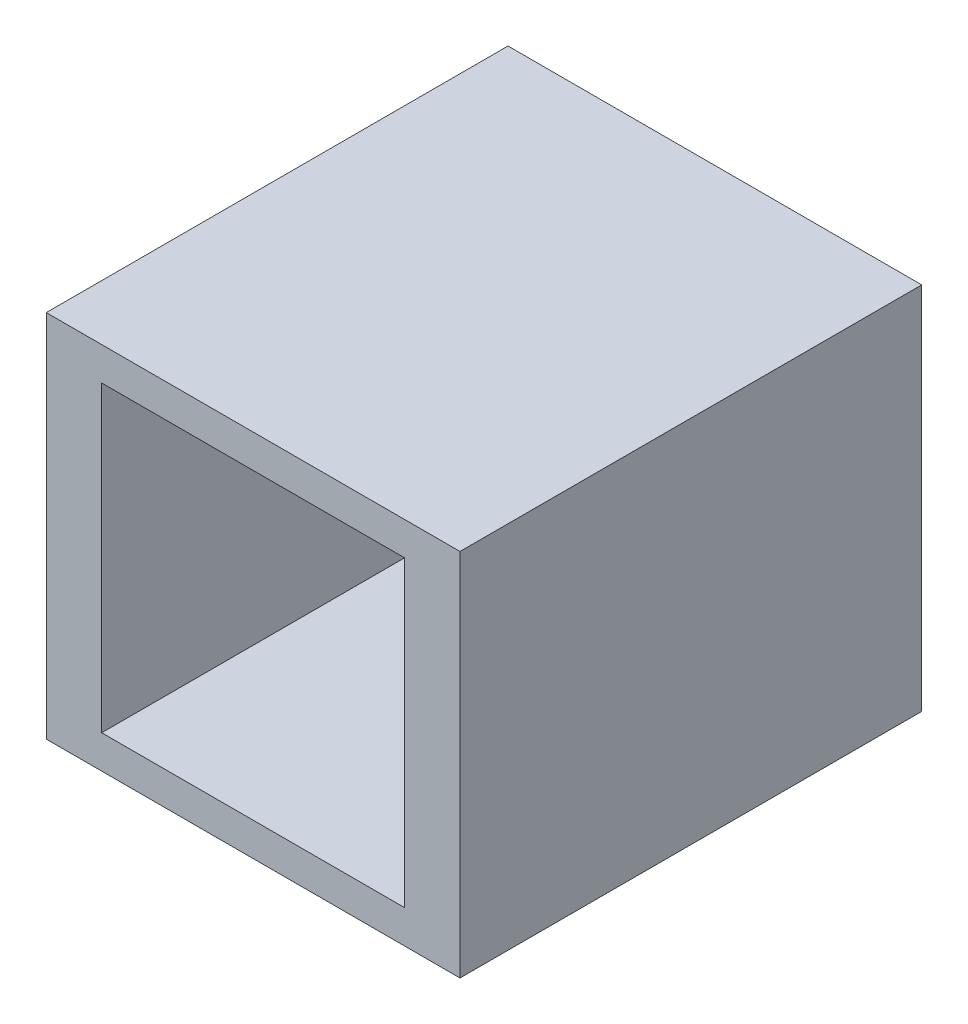
SolidWorks part; units mm, degrees
ref_plane "前视基准面" through (0, 0, 0) normal (0, 0, 1) x (1, 0, 0)
ref_plane "上视基准面" through (0, 0, 0) normal (0, 1, 0) x (1, 0, 0)
ref_plane "右视基准面" through (0, 0, 0) normal (1, 0, 0) x (0, 0, -1)
other "Configuration Table"
sketch "草图1" plane through (0, 0, 0) normal (0, 0, 1) x (1, 0, 0)
  line L5 (-17, -10) -> (17, -10)
  line L6 (-17, -10) -> (-17, 10)
  line L7 (-17, 10) -> (17, 10)
  line L8 (17, -10) -> (17, 10)
  line L9 (-17, -10) -> (17, 10) construction
  line L10 (-17, 10) -> (17, -10) construction
  line L11 (-8.2, -8.2) -> (8.2, -8.2)
  line L12 (-8.2, -8.2) -> (-8.2, 8.2)
  line L13 (-8.2, 8.2) -> (8.2, 8.2)
  line L14 (8.2, -8.2) -> (8.2, 8.2)
  line L15 (-8.2, -8.2) -> (8.2, 8.2) construction
  line L16 (-8.2, 8.2) -> (8.2, -8.2) construction
  line L17 (-11.2, -10) -> (11.2, -10)
  line L18 (-11.2, -10) -> (-11.2, 10)
  line L19 (-11.2, 10) -> (11.2, 10)
  line L20 (11.2, -10) -> (11.2, 10)
  line L21 (-11.2, -10) -> (11.2, 10) construction
  line L22 (-11.2, 10) -> (11.2, -10) construction
  point P0 (0, 0)
  point P9 (0, 0)
  dimension "D4" = 34
  dimension "D1" = 16.4
  dimension "D2" = 3
  dimension "D3" = 20
extrude "凸台-拉伸1" add sketch "草图1" along normal blind 20 contours L5 L20 L7 L18 L14 L11 L12 L13 region at (-10.8997, 0, 0)
extrude "凸台-拉伸2" add sketch "草图1<8>" against normal blind 5 contours L20 L19 L18 L17
sketch "草图1<8>" plane through (0, 0, 0) normal (0, 0, 1) x (1, 0, 0) same geometry as "草图1"
